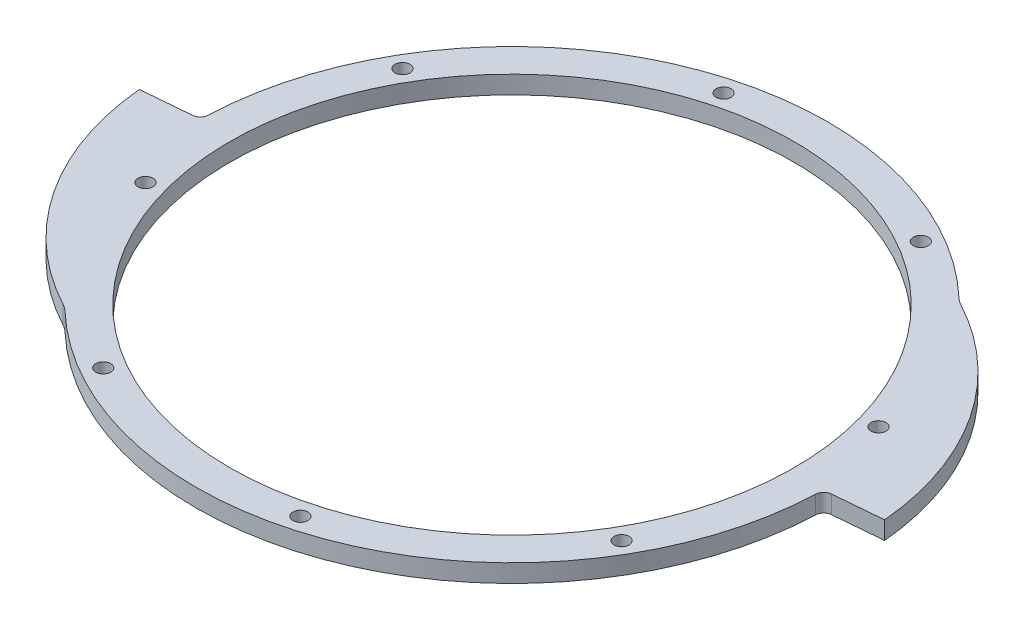
SolidWorks part; units mm, degrees
material "Alloy Steel"
ref_plane "Front Plane" through (0, 0, 0) normal (0, 0, 1) x (1, 0, 0)
ref_plane "Top Plane" through (0, 0, 0) normal (0, 1, 0) x (1, 0, 0)
ref_plane "Right Plane" through (0, 0, 0) normal (1, 0, 0) x (0, 0, -1)
sketch "Sketch1" plane through (0, 0, 0) normal (0, 1, 0) x (1, 0, 0)
  line L0 (0, 0) -> (-132, 0) construction
  line L1 (-132.0082, 0.0941) -> (-134.7743, 31.7103) construction
  line L2 (-111.9863, 1.751) -> (-132, 0)
  line L3 (-132, 0) -> (-132, 32.0934) construction
  line L4 (-129.3938, 0) -> (-182.8754, 0) construction
  line L5 (-112, 0) -> (-132, 0) construction
  line L6 (-79.4774, -79.4774) -> (0, 0) construction
  circle A0 centre (0, 0) radius 100
  arc A10 (-132, 0) -> (-79.4774, -79.4774) centre (-32.4231, 8.7118) ccw
  arc A11 (-79.4774, -79.4774) -> (-77.2845, -81.0624) centre (-84.1849, -88.3001) cw
  arc A12 (-77.2845, -81.0624) -> (-111.9863, 1.751) centre (0, 0) ccw
  dimension "D1" = 200
  dimension "D6" = 10
  dimension "D4" = 5
  dimension "D7" = 45
  dimension "D2" = 12
  dimension "D3" = 5
  dimension "D5" = 20
extrude "Boss-Extrude1" add sketch "Sketch1" along normal mid plane 6.35
fillet "Fillet1" radius 3 1 edges at (-111.9863, 0, -1.751)
pattern_circular "CirPattern1" count 2 over 360 about axis through (0, 3.175, 0) along (0, -1, 0) of "Boss-Extrude1", "Fillet1" reverse direction yes
sketch "Sketch2" plane through (0, 3.175, 0) normal (0, 1, 0) x (1, 0, 0)
  line L0 (-102.3881, -27.4348) -> (0, 0) construction
  line L1 (0, 0) -> (-106, 0) construction
  circle A0 centre (-102.3881, -27.4348) radius 2.65
  circle A2 centre (0, 0) radius 106 construction
  circle A3 centre (0, 0) radius 100 construction
  dimension "D3" = 5.3
  dimension "D1" = 106
  dimension "D2" = 6
  dimension "D4" = 15
extrude "Cut-Extrude1" cut sketch "Sketch2" against normal through all
pattern_circular "CirPattern2" count 8 over 360 about axis through (0, 3.175, 0) along (0, -1, 0) of "Cut-Extrude1"
equation "\"ring_id\"=200"
equation "\"D1@Sketch1\"=\"ring_id\""
equation "\"D2@Sketch2\"=\"D2@Sketch1\"/2"
